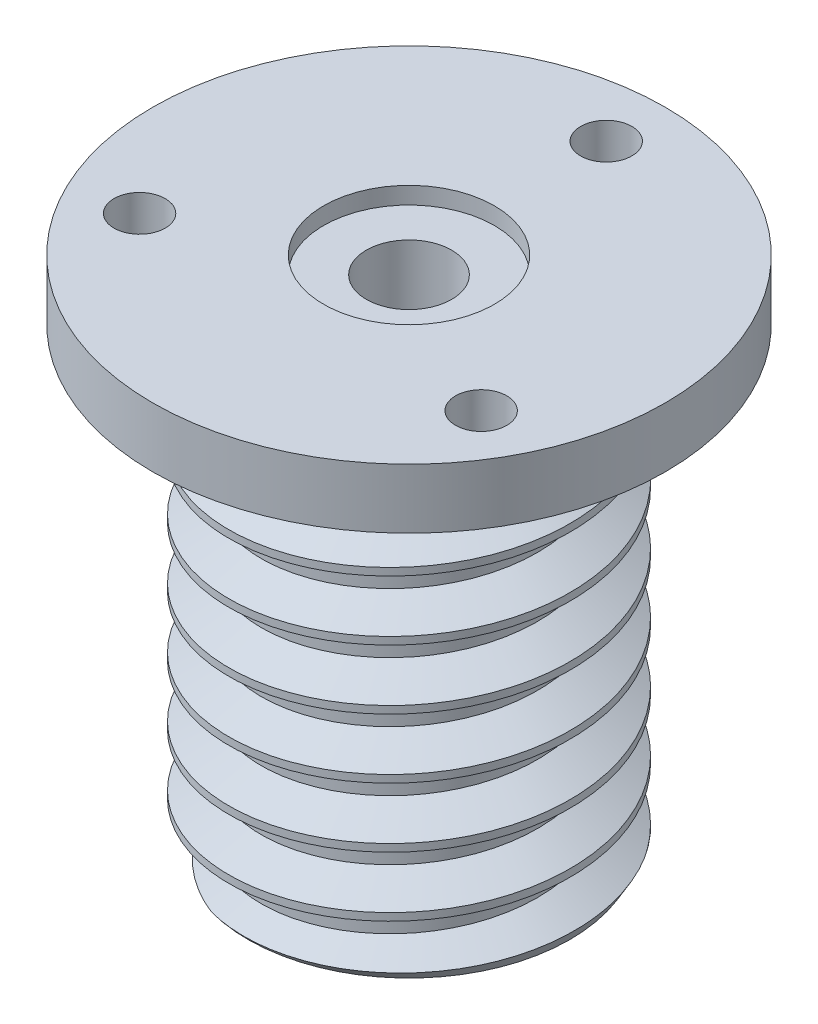
SolidWorks part; units mm, degrees
ref_plane "Front Plane" through (0, 0, 0) normal (0, 0, 1) x (1, 0, 0)
ref_plane "Top Plane" through (0, 0, 0) normal (0, 1, 0) x (1, 0, 0)
ref_plane "Right Plane" through (0, 0, 0) normal (1, 0, 0) x (0, 0, -1)
sketch "Sketch1" plane through (0, 0, 0) normal (1, 0, 0) x (0, 0, -1)
  line L2 (15, 30) -> (15, 26.5)
  line L3 (15, 26.5) -> (10, 26.5)
  line L4 (10, 23.825) -> (10, 0)
  line L6 (0, 0) -> (0, 30) construction
  line L7 (15, 30) -> (5, 30)
  line L8 (5, 30) -> (5, 29)
  line L9 (5, 29) -> (2.5, 29)
  line L10 (2.5, 29) -> (2.5, 1)
  line L11 (2.5, 1) -> (5, 1)
  line L12 (5, 1) -> (5, 0)
  line L13 (5, 0) -> (10, 0)
  line L14 (10, 26.5) -> (10, 23.825)
  dimension "D1" = 5
  dimension "D2" = 5
  dimension "D3" = 1
  dimension "D4" = 15
  dimension "D5" = 3.5
  dimension "D6" = 30
  dimension "D7" = 10
  dimension "D8" = 28
revolve "Revolve1" add sketch "Sketch1" angle 360 about L6
chamfer "Chamfer1" distance 1 angle 30 1 edges at (0, 0, -10) first distance on face at (0, 26.5, -10)
thread "Thread1" pitch 3.5 method cut profile "Thread Profile1" start angle 0, offset 0, length 26, pitch 3.5, diameter 20
ref_plane "Plane1" through (-10, 26.5, 0) normal (0, 0, 1) x (-1, 0, 0)
sketch "Thread Profile1" plane through (-10, 26.5, 0) normal (0, 0, 1) x (-1, 0, 0)
  line L0 (0, 0) -> (0, 3.5) construction
  line L11 (0, 0) -> (0, 3.0625)
  line L12 (0, 3.0625) -> (-1.8944, 1.9687)
  line L13 (-1.8944, 1.9687) -> (-1.8944, 1.0937)
  line L15 (-1.8944, 1.0937) -> (0, 0)
  line L17 (-1.8944, 1.5312) -> (0, 1.5312) construction
  point P2 (0, 0)
  dimension "Pitch" = 3.5
  dimension "Profile_Angle" = 60
  dimension "Profile_Land" = 0.875
  dimension "Profile_Height" = 1.8944
sketch "Sketch2" plane through (0, 30, 0) normal (0, 1, 0) x (1, 0, 0)
  line L1 (0, 11.547) -> (-10, -5.7735) construction
  line L2 (-10, -5.7735) -> (10, -5.7735) construction
  line L3 (10, -5.7735) -> (0, 11.547) construction
  circle A0 centre (0, 0) radius 5.7735 construction
  circle A1 centre (0, 11.547) radius 1.5
  circle A2 centre (10, -5.7735) radius 1.5
  circle A3 centre (-10, -5.7735) radius 1.5
  dimension "D2" = 3
  dimension "D1" = 20
extrude "Cut-Extrude1" cut sketch "Sketch2" against normal blind 4
